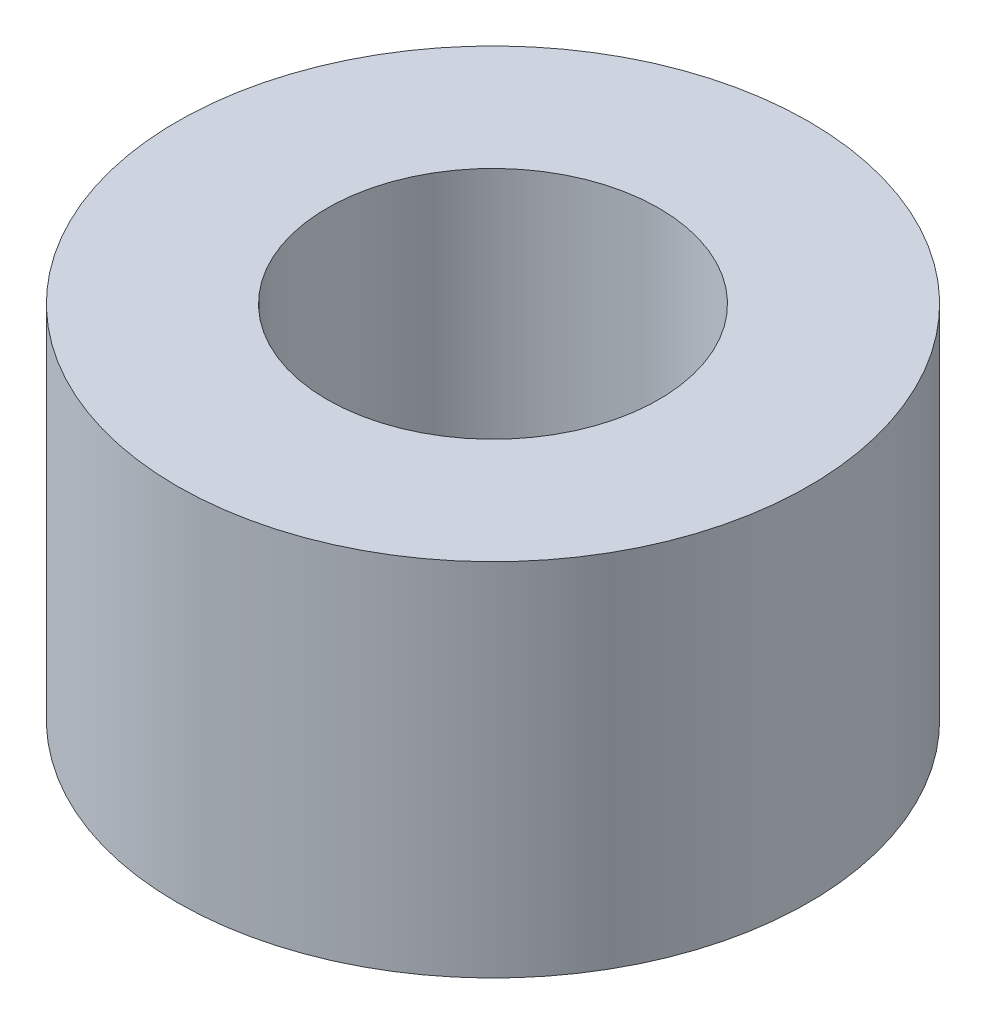
SolidWorks part; units mm, degrees
material "6061-T6 (SS)"
ref_plane "Front Plane" through (0, 0, 0) normal (0, 0, 1) x (1, 0, 0)
ref_plane "Top Plane" through (0, 0, 0) normal (0, 1, 0) x (1, 0, 0)
ref_plane "Right Plane" through (0, 0, 0) normal (1, 0, 0) x (0, 0, -1)
sketch "Sketch1" plane through (0, 0, 0) normal (0, 1, 0) x (1, 0, 0)
  circle A0 centre (0, 0) radius 3.81
  circle A1 centre (0, 0) radius 5.5626
  dimension "D1" = 7.62
  dimension "D2" = 11.1252
extrude "Boss-Extrude1" add sketch "Sketch1" along normal blind 6.35 contours A1
sketch "Sketch2" plane through (0, 0, 0) normal (0, -1, 0) x (1, 0, 0)
  circle A0 centre (0, 0) radius 2.921
  dimension "D1" = 5.842
extrude "Cut-Extrude1" cut sketch "Sketch2" against normal blind 6.35
